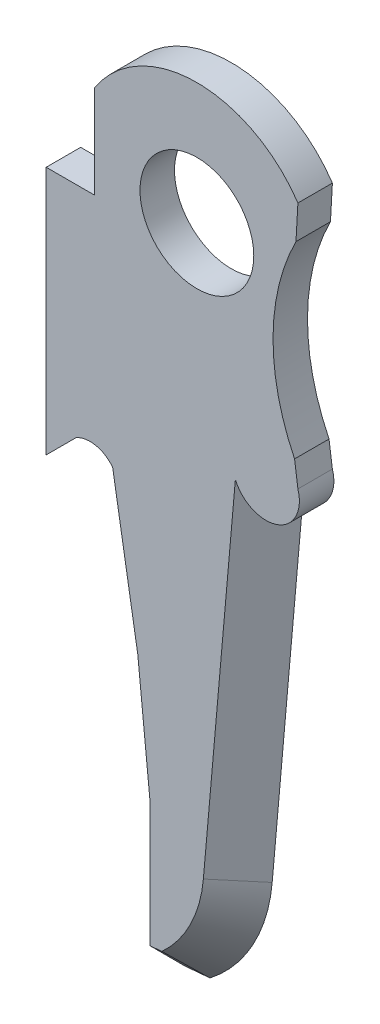
SolidWorks part; units mm, degrees
ref_plane "Front Plane" through (0, 0, 0) normal (0, 0, 1) x (1, 0, 0)
ref_plane "Top Plane" through (0, 0, 0) normal (0, 1, 0) x (1, 0, 0)
ref_plane "Right Plane" through (0, 0, 0) normal (1, 0, 0) x (0, 0, -1)
sketch "Sketch1" plane through (0, 0, 0) normal (0, 0, 1) x (1, 0, 0)
  line L0 (15.0593, 33.8835) -> (75.2966, 33.8835) construction
  line L1 (41.3336, 38.2646) -> (41.3336, 29.0885)
  line L2 (41.3336, 29.0885) -> (42.4357, 30.1905)
  line L3 (41.3336, 38.2646) -> (43.1116, 38.2646)
  line L4 (43.1116, 38.2646) -> (43.1116, 41.6832)
  line L5 (43.7819, 29.9141) -> (44.7072, 24.4104)
  line L6 (44.7072, 24.4104) -> (45.157, 19.9623)
  line L7 (45.157, 19.9623) -> (45.157, 14.0682)
  line L8 (49.5107, 31.05) -> (48.3876, 18.3429)
  line L9 (46.0975, 14.1501) -> (45.157, 14.0682)
  line L10 (50.6046, 32.638) -> (50.4816, 33.5349)
  line L11 (50.6046, 41.7597) -> (50.5333, 40.4917)
  arc A1 (46.0975, 14.1501) -> (48.3876, 18.3429) centre (42.4421, 18.8685) ccw
  arc A2 (43.7819, 29.9141) -> (42.4357, 30.1905) centre (42.9505, 29.2813) ccw
  arc A3 (50.6046, 41.7597) -> (43.1116, 41.6832) centre (46.8833, 39.26) ccw
  arc A4 (50.5333, 40.4917) -> (50.4816, 33.5349) centre (57.4831, 36.9615) ccw
  arc A5 (49.5107, 31.05) -> (50.6046, 32.638) centre (49.4291, 32.277) ccw
  point P11 (0, 0)
  dimension "D3" = 4.483
  dimension "D4" = 1.0448
  dimension "D5" = 7.795
  dimension "D6" = 1.2297
  dimension "D7" = 5.9686
  dimension "D1" = 9.271
  dimension "D2" = 1.778
  dimension "D8" = 9.1762
  dimension "D9" = 15.0202
extrude "Boss-Extrude1" add sketch "Sketch1" along normal blind 1.27
sketch "Sketch2" plane through (0, 0, 1.27) normal (0, 0, 1) x (1, 0, 0)
  circle A0 centre (46.8833, 39.26) radius 2.0955
  dimension "D1" = 4.191
extrude "Cut-Extrude1" cut sketch "Sketch2" against normal through all
chamfer "Chamfer1" distance 1.27 angle 45 3 edges at (45.6273, 14.1092, 1.27) (47.6803, 16.0074, 1.27) (48.9491, 24.6965, 1.27)
